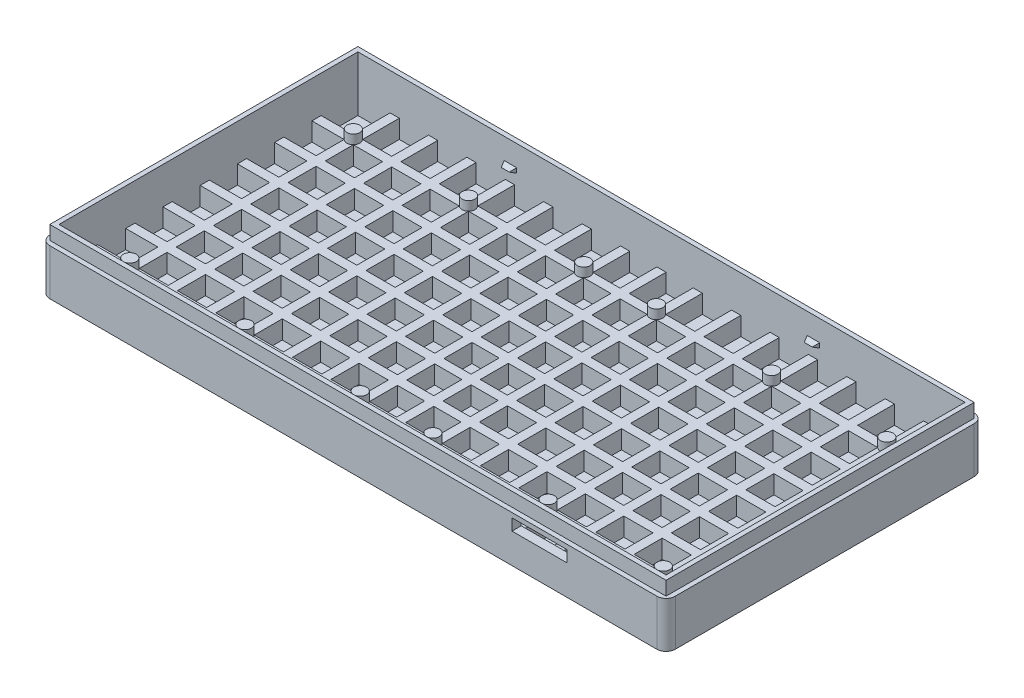
SolidWorks part; units mm, degrees
ref_plane "Front Plane" through (0, 0, 0) normal (0, 0, 1) x (1, 0, 0)
ref_plane "Top Plane" through (0, 0, 0) normal (0, 1, 0) x (1, 0, 0)
ref_plane "Right Plane" through (0, 0, 0) normal (1, 0, 0) x (0, 0, -1)
sketch "草图2" plane through (0, 0, 0) normal (0, 1, 0) x (1, 0, 0)
  line L1 (-66, 32.5) -> (66, 32.5)
  line L2 (-66, 32.5) -> (-66, -32.5)
  line L3 (-66, -32.5) -> (66, -32.5)
  line L4 (66, 32.5) -> (66, -32.5)
  line L5 (-66, 32.5) -> (66, -32.5) construction
  line L6 (-66, -32.5) -> (66, 32.5) construction
  line L15 (-66, 34.5) -> (66, 34.5)
  line L16 (-68, 32.5) -> (-68, -32.5)
  line L17 (-66, -34.5) -> (66, -34.5)
  line L18 (68, 32.5) -> (68, -32.5)
  line L19 (-68, 34.5) -> (68, -34.5) construction
  line L20 (-68, -34.5) -> (68, 34.5) construction
  arc A0 (-66, 34.5) -> (-68, 32.5) centre (-66, 32.5) ccw
  arc A1 (-68, -32.5) -> (-66, -34.5) centre (-66, -32.5) ccw
  arc A2 (66, -34.5) -> (68, -32.5) centre (66, -32.5) ccw
  arc A3 (66, 34.5) -> (68, 32.5) centre (66, 32.5) cw
  point P0 (0, 0)
  point P6 (0, 0)
  dimension "D5" = 2
  dimension "D1" = 132
  dimension "D2" = 65
  dimension "D3" = 136
  dimension "D4" = 69
extrude "凸台-拉伸2" add sketch "草图2" along normal blind 1 contours L2 L1 L4 L3
extrude "凸台-拉伸3" add sketch "草图2<3>" along normal blind 10
sketch "草图2<3>" plane through (0, 0, 0) normal (0, 1, 0) x (1, 0, 0) same geometry as "草图2"
sketch "草图3" plane through (0, 1, 0) normal (0, 1, 0) x (1, 0, 0)
  line L5 (-59, 32.5) -> (-57, 32.5)
  line L6 (-59, 32.5) -> (-59, -32.5)
  line L7 (-59, -32.5) -> (-57, -32.5)
  line L8 (-57, 32.5) -> (-57, -32.5)
  line L9 (-66, 32.5) -> (66, 32.5) construction
  line L10 (-66, 32.5) -> (-66, -32.5) construction
  line L19 (-34.1, 32.5) -> (-32.1, 32.5)
  line L20 (-32.1, 32.5) -> (-32.1, -32.5)
  line L21 (-34.1, -32.5) -> (-32.1, -32.5)
  line L66 (66, 32.5) -> (-66, 32.5) construction
  line L67 (-66, 24.5) -> (66, 24.5)
  line L68 (-66, 24.5) -> (-66, 22.5)
  line L69 (-66, 22.5) -> (66, 22.5)
  line L70 (66, 24.5) -> (66, 22.5)
  line L71 (-66, 16.4) -> (-66, 14.4)
  line L72 (-66, 16.4) -> (66, 16.4)
  line L73 (66, 16.4) -> (66, 14.4)
  line L74 (-66, 14.4) -> (66, 14.4)
  line L75 (-66, 8.3) -> (-66, 6.3)
  line L76 (-66, 8.3) -> (66, 8.3)
  line L77 (66, 8.3) -> (66, 6.3)
  line L78 (-66, 6.3) -> (66, 6.3)
  line L79 (-66, 0.2) -> (-66, -1.8)
  line L80 (-66, 0.2) -> (66, 0.2)
  line L81 (66, 0.2) -> (66, -1.8)
  line L82 (-66, -1.8) -> (66, -1.8)
  line L83 (-66, -7.9) -> (-66, -9.9)
  line L84 (-66, -7.9) -> (66, -7.9)
  line L85 (66, -7.9) -> (66, -9.9)
  line L86 (-66, -9.9) -> (66, -9.9)
  line L87 (-66, -16) -> (-66, -18)
  line L88 (-66, -16) -> (66, -16)
  line L89 (66, -16) -> (66, -18)
  line L90 (-66, -18) -> (66, -18)
  line L91 (-66, -24.1) -> (-66, -26.1)
  line L92 (-66, -24.1) -> (66, -24.1)
  line L93 (66, -24.1) -> (66, -26.1)
  line L94 (-66, -26.1) -> (66, -26.1)
  line L95 (-50.7, 32.5) -> (-50.7, -32.5) [skipped]
  line L96 (-50.7, -32.5) -> (-48.7, -32.5) [skipped]
  line L97 (-48.7, 32.5) -> (-48.7, -32.5) [skipped]
  line L98 (-50.7, 32.5) -> (-48.7, 32.5) [skipped]
  line L99 (-42.4, 32.5) -> (-42.4, -32.5) [skipped]
  line L100 (-42.4, -32.5) -> (-40.4, -32.5) [skipped]
  line L101 (-40.4, 32.5) -> (-40.4, -32.5) [skipped]
  line L102 (-42.4, 32.5) -> (-40.4, 32.5) [skipped]
  line L103 (-34.1, 32.5) -> (-34.1, -32.5) [skipped]
  line L104 (-25.8, 32.5) -> (-25.8, -32.5) [skipped]
  line L105 (-25.8, -32.5) -> (-23.8, -32.5) [skipped]
  line L106 (-23.8, 32.5) -> (-23.8, -32.5) [skipped]
  line L107 (-25.8, 32.5) -> (-23.8, 32.5) [skipped]
  line L108 (-9.2, 32.5) -> (-9.2, -32.5) [skipped]
  line L109 (-9.2, -32.5) -> (-7.2, -32.5) [skipped]
  line L110 (-7.2, 32.5) -> (-7.2, -32.5) [skipped]
  line L111 (-9.2, 32.5) -> (-7.2, 32.5) [skipped]
  line L112 (-17.5, 32.5) -> (-17.5, -32.5) [skipped]
  line L113 (-17.5, -32.5) -> (-15.5, -32.5) [skipped]
  line L114 (-15.5, 32.5) -> (-15.5, -32.5) [skipped]
  line L115 (-17.5, 32.5) -> (-15.5, 32.5) [skipped]
  line L116 (-0.9, 32.5) -> (-0.9, -32.5) [skipped]
  line L117 (-0.9, -32.5) -> (1.1, -32.5) [skipped]
  line L118 (1.1, 32.5) -> (1.1, -32.5) [skipped]
  line L119 (-0.9, 32.5) -> (1.1, 32.5) [skipped]
  line L120 (7.4, 32.5) -> (7.4, -32.5) [skipped]
  line L121 (7.4, -32.5) -> (9.4, -32.5) [skipped]
  line L122 (9.4, 32.5) -> (9.4, -32.5) [skipped]
  line L123 (7.4, 32.5) -> (9.4, 32.5) [skipped]
  line L124 (15.7, 32.5) -> (15.7, -32.5) [skipped]
  line L125 (15.7, -32.5) -> (17.7, -32.5) [skipped]
  line L126 (17.7, 32.5) -> (17.7, -32.5) [skipped]
  line L127 (15.7, 32.5) -> (17.7, 32.5) [skipped]
  line L128 (24, 32.5) -> (24, -32.5) [skipped]
  line L129 (24, -32.5) -> (26, -32.5) [skipped]
  line L130 (26, 32.5) -> (26, -32.5) [skipped]
  line L131 (24, 32.5) -> (26, 32.5) [skipped]
  line L132 (32.3, 32.5) -> (32.3, -32.5) [skipped]
  line L133 (32.3, -32.5) -> (34.3, -32.5) [skipped]
  line L134 (34.3, 32.5) -> (34.3, -32.5) [skipped]
  line L135 (32.3, 32.5) -> (34.3, 32.5) [skipped]
  line L136 (40.6, 32.5) -> (40.6, -32.5) [skipped]
  line L137 (40.6, -32.5) -> (42.6, -32.5) [skipped]
  line L138 (42.6, 32.5) -> (42.6, -32.5) [skipped]
  line L139 (40.6, 32.5) -> (42.6, 32.5) [skipped]
  line L140 (48.9, 32.5) -> (48.9, -32.5) [skipped]
  line L141 (48.9, -32.5) -> (50.9, -32.5) [skipped]
  line L142 (50.9, 32.5) -> (50.9, -32.5) [skipped]
  line L143 (48.9, 32.5) -> (50.9, 32.5) [skipped]
  line L144 (57.2, 32.5) -> (57.2, -32.5) [skipped]
  line L145 (57.2, -32.5) -> (59.2, -32.5) [skipped]
  line L146 (59.2, 32.5) -> (59.2, -32.5) [skipped]
  line L147 (57.2, 32.5) -> (59.2, 32.5) [skipped]
  line L148 (57, 32.5) -> (59, 32.5)
  line L149 (57, 32.5) -> (57, -32.5)
  line L150 (57, -32.5) -> (59, -32.5)
  line L151 (59, 32.5) -> (59, -32.5)
  line L152 (66, 32.5) -> (66, -32.5) construction
  line L153 (-50.65, 32.5) -> (-50.65, -32.5)
  line L154 (-50.65, 32.5) -> (-48.65, 32.5)
  line L155 (-48.65, 32.5) -> (-48.65, -32.5)
  line L156 (-50.65, -32.5) -> (-48.65, -32.5)
  line L157 (-42.3, 32.5) -> (-42.3, -32.5)
  line L158 (-42.3, 32.5) -> (-40.3, 32.5)
  line L159 (-40.3, 32.5) -> (-40.3, -32.5)
  line L160 (-42.3, -32.5) -> (-40.3, -32.5)
  line L161 (-33.95, 32.5) -> (-33.95, -32.5)
  line L162 (-33.95, 32.5) -> (-31.95, 32.5)
  line L163 (-31.95, 32.5) -> (-31.95, -32.5)
  line L164 (-33.95, -32.5) -> (-31.95, -32.5)
  line L165 (-25.6, 32.5) -> (-25.6, -32.5)
  line L166 (-25.6, 32.5) -> (-23.6, 32.5)
  line L167 (-23.6, 32.5) -> (-23.6, -32.5)
  line L168 (-25.6, -32.5) -> (-23.6, -32.5)
  line L169 (-17.25, 32.5) -> (-17.25, -32.5)
  line L170 (-17.25, 32.5) -> (-15.25, 32.5)
  line L171 (-15.25, 32.5) -> (-15.25, -32.5)
  line L172 (-17.25, -32.5) -> (-15.25, -32.5)
  line L173 (-8.9, 32.5) -> (-8.9, -32.5)
  line L174 (-8.9, 32.5) -> (-6.9, 32.5)
  line L175 (-6.9, 32.5) -> (-6.9, -32.5)
  line L176 (-8.9, -32.5) -> (-6.9, -32.5)
  line L177 (48.65, 32.5) -> (50.65, 32.5)
  line L178 (50.65, 32.5) -> (50.65, -32.5)
  line L179 (48.65, -32.5) -> (50.65, -32.5)
  line L180 (48.65, 32.5) -> (48.65, -32.5)
  line L181 (40.3, 32.5) -> (42.3, 32.5)
  line L182 (42.3, 32.5) -> (42.3, -32.5)
  line L183 (40.3, -32.5) -> (42.3, -32.5)
  line L184 (40.3, 32.5) -> (40.3, -32.5)
  line L185 (31.95, 32.5) -> (33.95, 32.5)
  line L186 (33.95, 32.5) -> (33.95, -32.5)
  line L187 (31.95, -32.5) -> (33.95, -32.5)
  line L188 (31.95, 32.5) -> (31.95, -32.5)
  line L189 (23.6, 32.5) -> (25.6, 32.5)
  line L190 (25.6, 32.5) -> (25.6, -32.5)
  line L191 (23.6, -32.5) -> (25.6, -32.5)
  line L192 (23.6, 32.5) -> (23.6, -32.5)
  line L193 (15.25, 32.5) -> (17.25, 32.5)
  line L194 (17.25, 32.5) -> (17.25, -32.5)
  line L195 (15.25, -32.5) -> (17.25, -32.5)
  line L196 (15.25, 32.5) -> (15.25, -32.5)
  line L197 (6.9, 32.5) -> (8.9, 32.5)
  line L198 (8.9, 32.5) -> (8.9, -32.5)
  line L199 (6.9, -32.5) -> (8.9, -32.5)
  line L200 (6.9, 32.5) -> (6.9, -32.5)
  line L201 (-1, 32.5) -> (-1, -32.5)
  line L202 (-1, 32.5) -> (1, 32.5)
  line L203 (1, 32.5) -> (1, -32.5)
  line L204 (-1, -32.5) -> (1, -32.5)
  dimension "D1" = 2
  dimension "D2" = 65
  dimension "D3" = 7
  dimension "D5" = 2
  dimension "D6" = 132
  dimension "D7" = 8
  dimension "D9" = 2
  dimension "D10" = 7
  dimension "D4" = 15
  dimension "D8" = 7
  dimension "D11" = 7
  dimension "D12" = 7
extrude "栅格" add sketch "草图3" along normal blind 4 contours L67 L70 L69 L68 | L72 L73 L74 L71 | L78 L77 L76 L75 | L80 L81 L82 L79 | L86 L85 L84 L83 | L88 L89 L90 L87 | L94 L93 L92 L91 | L8 L7 L6 L5 | L153 L156 L155 L154 | L157 L160 L159 L158 | L161 L164 L163 L162 | L165 L168 L167 L166 | L169 L172 L171 L170 | L173 L176 L175 L174 | L201 L204 L203 L202 | L200 L199 L198 L197 | L196 L195 L194 L193 | L192 L191 L190 L189 | L188 L187 L186 L185 | L184 L183 L182 L181 | L180 L179 L178 L177 | L149 L150 L151 L148
sketch "草图4" plane through (0, 5, 0) normal (0, 1, 0) x (1, 0, 0)
  line L17 (-59, -18) -> (-59, -24.1) construction
  line L18 (-66, -24.1) -> (-59, -24.1) construction
  line L19 (57, 32.5) -> (57, 24.5) construction
  line L20 (50.65, 24.5) -> (57, 24.5) construction
  line L21 (57, -18) -> (57, -24.1) construction
  line L22 (50.65, -24.1) -> (57, -24.1) construction
  circle B0 centre (-58, 23.5) radius 1.4
  circle B1 centre (-32.95, 23.5) radius 1.4
  circle B2 centre (-7.9, 23.5) radius 1.4
  circle B3 centre (-58, -25.1) radius 1.4
  circle B4 centre (-32.95, -25.1) radius 1.4
  circle B5 centre (-7.9, -25.1) radius 1.4
  circle B6 centre (7.9, 23.5) radius 1.4
  circle B7 centre (32.95, 23.5) radius 1.4
  circle B8 centre (58, 23.5) radius 1.4
  circle B9 centre (7.9, -25.1) radius 1.4
  circle B10 centre (32.95, -25.1) radius 1.4
  circle B11 centre (58, -25.1) radius 1.4
  dimension "D1" = 1
  dimension "D3" = 1
  dimension "D2" = 1
  dimension "D4" = 1
  dimension "D5" = 1
  dimension "D6" = 1
sketch_block_instance "块2-1"
sketch_block "块2"
sketch_block_instance "块2-2"
sketch_block_instance "块2-3"
sketch_block_instance "块2-4"
extrude "卡座" add sketch "草图4" along normal blind 2
sketch "草图5" plane through (0, 0, -32.5) normal (0, 0, 1) x (1, 0, 0)
  line L0 (-33.95, 5) -> (-31.95, 5) construction
  line L1 (-34.2214, 8.4323) -> (-31.4795, 8.4323)
  line L2 (-34.2214, 8.4323) -> (-34.2214, 7.4)
  line L3 (-34.2214, 7.4) -> (-31.4795, 7.4)
  line L4 (-31.4795, 8.4323) -> (-31.4795, 7.4)
  line L5 (-34.2214, 8.4323) -> (-31.4795, 7.4) construction
  line L6 (-34.2214, 7.4) -> (-31.4795, 8.4323) construction
  line L7 (31.6635, 8.4323) -> (34.4055, 8.4323)
  line L8 (31.6635, 8.4323) -> (31.6635, 7.4)
  line L9 (31.6635, 7.4) -> (34.4055, 7.4)
  line L10 (34.4055, 8.4323) -> (34.4055, 7.4)
  line L11 (66, 10) -> (-66, 10) construction
  line L12 (-66, 10) -> (-66, 1) construction
  point P0 (-32.8504, 7.9161)
  dimension "D1" = 2.4
  dimension "D2" = 2.6
  dimension "D3" = 1.0323
  dimension "D4" = 2.742
  dimension "D5" = 31.7786
extrude "凸台-拉伸5" add sketch "草图5" along normal blind 10 draft 25
sketch "草图7" plane through (0, 10, 0) normal (0, 1, 0) x (1, 0, 0)
  line L0 (-66, 32.5) -> (-66, -32.5) construction
  line L1 (-67, 33.5) -> (67, 33.5)
  line L2 (-67, 33.5) -> (-67, -33.5)
  line L3 (-67, -33.5) -> (67, -33.5)
  line L4 (67, 33.5) -> (67, -33.5)
  line L5 (66, 32.5) -> (-66, 32.5) construction
  line L7 (-66, 32.5) -> (66, 32.5)
  line L8 (-66, 32.5) -> (-66, -32.5)
  line L9 (-66, -32.5) -> (66, -32.5)
  line L10 (66, 32.5) -> (66, -32.5)
  dimension "D1" = 134
  dimension "D2" = 67
  dimension "D3" = 1
  dimension "D4" = 1
extrude "凸台-拉伸6" add sketch "草图7" along normal blind 3
sketch "草图8" plane through (0, 0, 32.5) normal (0, 0, -1) x (-1, 0, 0)
  line L0 (-66, 13) -> (-66, 1) construction
  line L1 (-34.5, 6.5) -> (-46.5, 6.5)
  line L2 (-34.5, 6.5) -> (-34.5, 9)
  line L3 (-34.5, 9) -> (-46.5, 9)
  line L4 (-46.5, 6.5) -> (-46.5, 9)
  line L5 (66, 13) -> (-66, 13) construction
  dimension "D1" = 19.5
  dimension "D2" = 12
  dimension "D3" = 2.5
  dimension "D4" = 4
extrude "切除-拉伸1" cut sketch "草图8" against normal up to next
ref_plane "基准面1" through (46.5, 9, 32.5) normal (0, -1, 0) x (-1, 0, 0)
sketch "草图9" plane through (46.5, 9, 32.5) normal (0, -1, 0) x (1, 0, 0)
